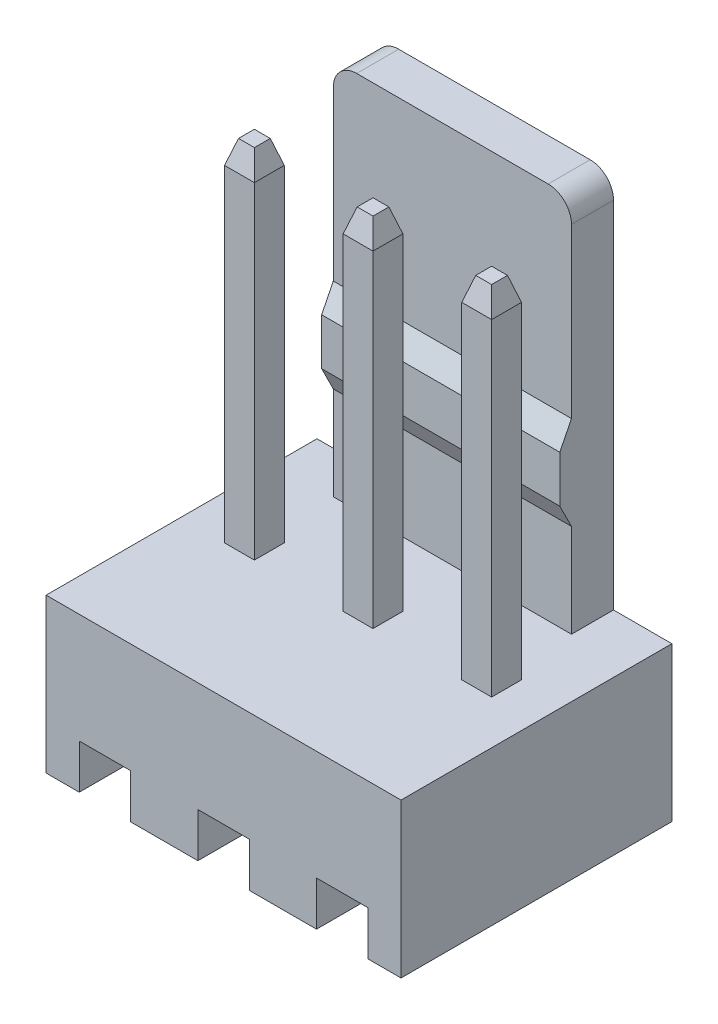
SolidWorks part; units mm, degrees
ref_plane "Front" through (0, 0, 0) normal (0, 0, 1) x (1, 0, 0)
ref_plane "Top" through (0, 0, 0) normal (0, 1, 0) x (1, 0, 0)
ref_plane "Right" through (0, 0, 0) normal (1, 0, 0) x (0, 0, -1)
sketch "Sketch1" plane through (0, 0, 0) normal (1, 0, 0) x (0, 0, -1)
  line L0 (0, 21.2983) -> (0, 0) construction
  line L1 (-20.5977, 0) -> (-7.1534, 0) construction
  line L2 (2.6, 0) -> (2.6, 11.4)
  line L3 (-3.2, 0) -> (2.6, 0)
  line L4 (-3.2, 0) -> (-3.2, 3.3)
  line L5 (-3.2, 3.3) -> (1.7, 3.3)
  line L6 (-1.2887, 6.3) -> (3.9473, 6.3) construction
  line L7 (2.6, 11.4) -> (1.7, 11.4)
  line L8 (1.7, 11.4) -> (1.7, 7.3)
  line L9 (1.7, 7.3) -> (1.45, 6.8)
  line L10 (1.45, 6.8) -> (1.45, 5.8)
  line L11 (1.45, 5.8) -> (1.7, 5.3)
  line L12 (1.7, 5.3) -> (1.7, 3.3)
  dimension "D1" = 3.3
  dimension "D2" = 5.8
  dimension "D3" = 1.45
  dimension "D4" = 2
  dimension "D5" = 3
  dimension "D6" = 1
  dimension "D7" = 0.9
  dimension "D8" = 11.4
  dimension "D9" = 3.2
extrude "Base-Extrude" add sketch "Sketch1" along normal mid plane 7.6
sketch "Sketch2" plane through (0, 0, -2.6) normal (0, 0, -1) x (-1, 0, 0)
  line L0 (0, 12.5423) -> (0, 0) construction
  line L1 (-3.8, 3.3) -> (3.8, 3.3) construction
  line L2 (2.55, 12.4) -> (4.8, 12.4)
  line L3 (2.55, 12.4) -> (2.55, 3.3)
  line L4 (2.55, 3.3) -> (4.8, 3.3)
  line L5 (4.8, 12.4) -> (4.8, 3.3)
  line L6 (-3.8, 11.4) -> (3.8, 11.4) construction
  line L7 (3.8, 0) -> (3.8, 11.4) construction
  line L8 (-4.8, 12.4) -> (-4.8, 3.3)
  line L9 (-2.55, 3.3) -> (-4.8, 3.3)
  line L10 (-2.55, 12.4) -> (-2.55, 3.3)
  line L11 (-2.55, 12.4) -> (-4.8, 12.4)
  line L12 (-3.8, 0) -> (3.8, 0) construction
  line L13 (-0.55, 0.95) -> (0.55, 0.95)
  line L14 (-0.55, 0.95) -> (-0.55, 0)
  line L15 (-0.55, 0) -> (0.55, 0)
  line L16 (0.55, 0.95) -> (0.55, 0)
  line L17 (3.09, 0.95) -> (3.09, 0)
  line L18 (1.99, 0.95) -> (3.09, 0.95)
  line L19 (1.99, 0.95) -> (1.99, 0)
  line L20 (1.99, 0) -> (3.09, 0)
  line L21 (0.55, 0.95) -> (3.09, 0.95) construction
  line L22 (-1.99, 0) -> (-3.09, 0)
  line L23 (-1.99, 0.95) -> (-1.99, 0)
  line L24 (-1.99, 0.95) -> (-3.09, 0.95)
  line L25 (-3.09, 0.95) -> (-3.09, 0)
  dimension "D1" = 5.1
  dimension "D2" = 1
  dimension "D3" = 1
  dimension "D4" = 1.1
  dimension "D5" = 2.35
  dimension "D6" = 2.54
extrude "Cut-Extrude1" cut sketch "Sketch2" against normal through all
fillet "Fillet1" radius 0.5 2 edges at (-2.55, 11.4, -2.15) (2.55, 11.4, -2.15)
sketch "Sketch3" plane through (0, 3.3, 0) normal (0, 1, 0) x (-1, 0, 0)
  line L0 (-5.252, 0) -> (5.635, 0) construction
  line L1 (0, 3.862) -> (0, -2.7966) construction
  line L2 (2.22, 0.32) -> (2.86, 0.32)
  line L3 (-0.32, 0.32) -> (0.32, 0.32)
  line L4 (-0.32, 0.32) -> (-0.32, -0.32)
  line L5 (-0.32, -0.32) -> (0.32, -0.32)
  line L6 (0.32, 0.32) -> (0.32, -0.32)
  line L7 (2.22, 0.32) -> (2.22, -0.32)
  line L8 (2.22, -0.32) -> (2.86, -0.32)
  line L9 (2.86, 0.32) -> (2.86, -0.32)
  line L10 (-0.32, 0.32) -> (2.22, 0.32) construction
  line L11 (-2.22, 0.32) -> (-2.86, 0.32)
  line L12 (-2.22, 0.32) -> (-2.22, -0.32)
  line L13 (-2.22, -0.32) -> (-2.86, -0.32)
  line L14 (-2.86, -0.32) -> (-2.86, 0.32)
  dimension "D1" = 0.64
  dimension "D2" = 2.54
extrude "Boss-Extrude1" add sketch "Sketch3" along normal offset from surface (7.5 mm away) 10.8 up to face at (3.445, 0, 0.3)
chamfer "Chamfer1" distance 0.5 distance2 0.15 12 edges at (2.86, 10.8, 0) (2.54, 10.8, 0.32) (2.22, 10.8, 0) (2.54, 10.8, -0.32) (-2.86, 10.8, 0) (-2.54, 10.8, -0.32) (-2.22, 10.8, 0) (-2.54, 10.8, 0.32) (-0.32, 10.8, 0) (0, 10.8, -0.32) (0.32, 10.8, 0) (0, 10.8, 0.32) first distance on face at (2.86, 7.05, 0) first distance on face at (2.54, 7.05, 0.32) first distance on face at (2.22, 7.05, 0) first distance on face at (2.54, 7.05, -0.32) first distance on face at (-2.86, 7.05, 0) first distance on face at (-2.54, 7.05, -0.32) first distance on face at (-2.22, 7.05, 0) first distance on face at (-2.54, 7.05, 0.32) first distance on face at (-0.32, 7.05, 0) first distance on face at (0, 7.05, -0.32) first distance on face at (0.32, 7.05, 0) first distance on face at (0, 7.05, 0.32)
sketch "Place Sketch***" plane through (0, 0, 0) normal (0, -1, 0) x (1, 0, 0)
  line L0 (3.8, 0) -> (-3.8, 0) construction
  line L1 (3.8, 3.2) -> (-3.8, 3.2)
  line L2 (3.8, 3.2) -> (3.8, -2.6)
  line L3 (3.8, -2.6) -> (-3.8, -2.6)
  line L4 (-3.8, 3.2) -> (-3.8, -2.6)
  line L5 (0, 3.2) -> (0, -2.6) construction
other "CPoint1" parameters "Diameter"=5, "StubLength"=7
ref_axis "Axis1" through (0, -10, 0) along (0, 1, 0)
